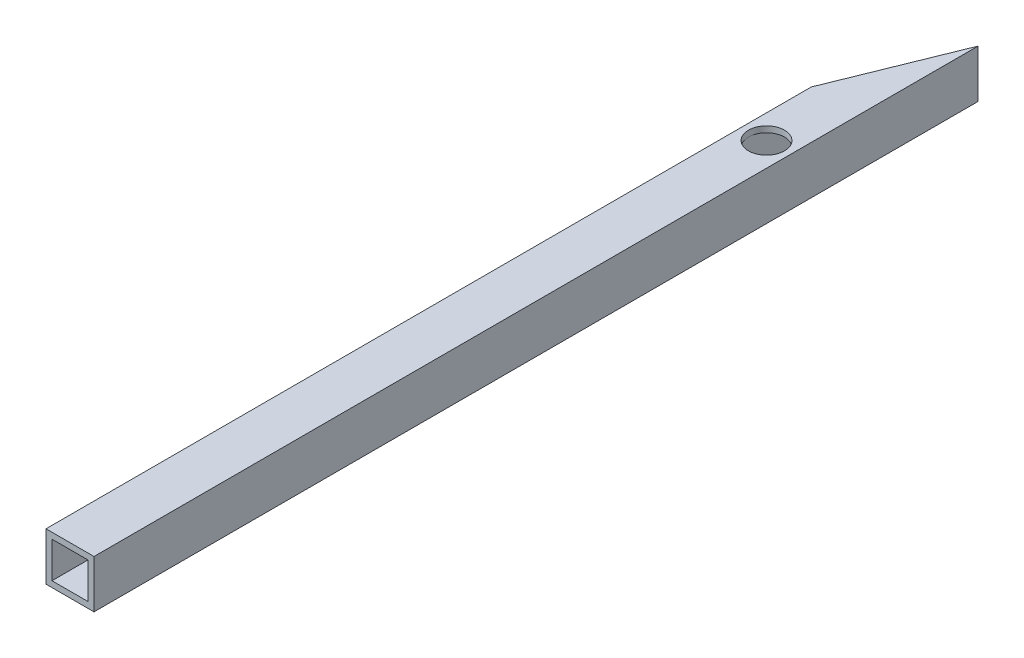
SolidWorks part; units mm, degrees
ref_plane "Front Plane" through (0, 0, 0) normal (0, 0, 1) x (1, 0, 0)
ref_plane "Top Plane" through (0, 0, 0) normal (0, 1, 0) x (1, 0, 0)
ref_plane "Right Plane" through (0, 0, 0) normal (1, 0, 0) x (0, 0, -1)
sketch "Sketch1" plane through (0, 0, 0) normal (0, 0, 1) x (1, 0, 0)
  line L0 (-9.525, 9.525) -> (9.525, 9.525)
  line L2 (-12.7, 12.7) -> (12.7, 12.7)
  line L3 (-12.7, 12.7) -> (-12.7, -12.7)
  line L4 (-12.7, -12.7) -> (12.7, -12.7)
  line L5 (12.7, 12.7) -> (12.7, -12.7)
  line L10 (9.525, 9.525) -> (9.525, -9.525)
  line L11 (-9.525, -9.525) -> (9.525, -9.525)
  line L12 (-9.525, 9.525) -> (-9.525, -9.525)
  point P12 (0, 12.7)
  point P14 (12.7, 0)
  dimension "Wall Thickness" = 3.175
  dimension "Outside Width" = 25.4
  dimension "Outside Height" = 25.4
  dimension "Inside Height" = 19.05
  dimension "Inside Width" = 19.05
sketch "Sketch2" plane through (0, 0, 0) normal (1, 0, 0) x (0, 0, -1)
  line L0 (241.3, 0) -> (-241.3, 0)
  point P4 (0, 0)
  point P7 (-241.3, 0)
  point P10 (241.3, 0)
  dimension "Length" = 482.6
sketch "Sketch3" plane through (0, 0, 0) normal (0, 0, 1) x (1, 0, 0)
  line L21 (12.7, 12.7) -> (-12.7, 12.7)
  line L22 (12.7, -12.7) -> (12.7, 12.7)
  line L23 (-12.7, -12.7) -> (12.7, -12.7)
  line L24 (-12.7, 12.7) -> (-12.7, -12.7)
  line L25 (12.7, 12.7) -> (-12.7, 12.7)
  line L26 (12.7, -12.7) -> (12.7, 12.7)
  line L27 (-12.7, -12.7) -> (12.7, -12.7)
  line L28 (-12.7, 12.7) -> (-12.7, -12.7)
  line L29 (9.525, 9.525) -> (-9.525, 9.525)
  line L30 (9.525, -9.525) -> (9.525, 9.525)
  line L31 (-9.525, -9.525) -> (9.525, -9.525)
  line L32 (-9.525, 9.525) -> (-9.525, -9.525)
  line L33 (9.525, 9.525) -> (-9.525, 9.525)
  line L34 (9.525, -9.525) -> (9.525, 9.525)
  line L35 (-9.525, -9.525) -> (9.525, -9.525)
  line L36 (-9.525, 9.525) -> (-9.525, -9.525)
  dimension "D1" = 0
  dimension "D2" = 0
extrude "Boss-Extrude1" add sketch "Sketch3" along normal up to vertex (241.3 mm away) and the other way up to vertex (241.3 mm away) up to point (0, 0, 241.3) other way up to point (0, 0, -241.3)
sketch "Drawing Reference" plane through (0, 0, 0) normal (1, 0, 0) x (0, 0, -1)
  line L0 (-241.3, 0) -> (241.3, 0) construction
  line L1 (0, -12.7) -> (0, 12.7) construction
  line L2 (-241.3, -12.7) -> (241.3, -12.7) construction
  line L5 (-241.3, 12.7) -> (241.3, 12.7) construction
  point P7 (-223.012, 0)
  point P8 (223.012, 0)
  dimension "D1" = 18.288
sketch "Sketch4" plane through (0, 12.7, 0) normal (0, 1, 0) x (1, 0, 0)
  line L0 (-12.7, 163.7026) -> (12.7, 226.5698)
  line L1 (-191.8254, -279.6484) -> (42.7916, 301.0491) construction
  line L2 (-12.7, -241.3) -> (-12.7, 241.3) construction
  line L3 (12.7, -241.3) -> (12.7, 241.3) construction
  line L4 (-12.7, 163.7026) -> (-12.7, 241.3)
  line L5 (-12.7, 241.3) -> (12.7, 241.3)
  line L6 (12.7, 241.3) -> (12.7, 226.5698)
  line L7 (-12.7, 163.7026) -> (10.8505, 154.1876) construction
  line L8 (0, 241.3) -> (0, -241.3) construction
  line L9 (12.7, -241.3) -> (-12.7, -241.3) construction
  line L10 (10.8505, 154.1876) -> (0, 127.3317) construction
  circle A0 centre (0, 127.3317) radius 9.525
  dimension "D1" = 25.4
extrude "Cut-Extrude1" cut sketch "Sketch4" against normal blind 25.4
equation "\"D1@Drawing Reference\"=\"Outside Width@Sketch1\" * 0.72"
